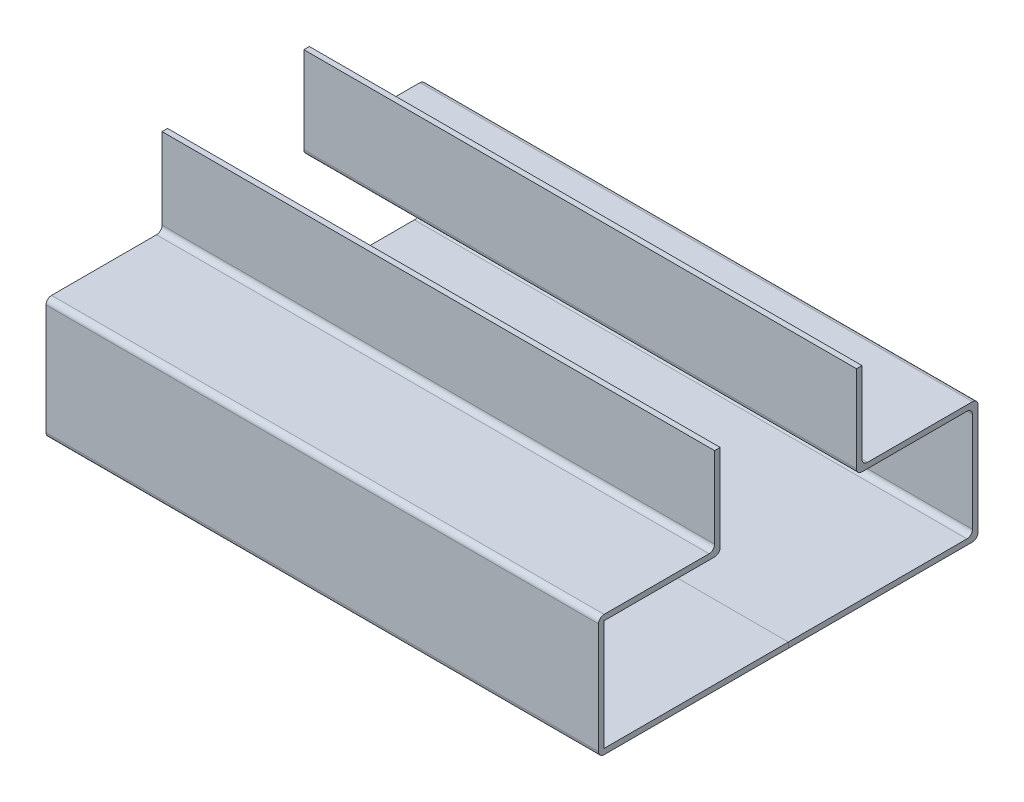
SolidWorks part; units mm, degrees
ref_plane "前基準面" through (0, 0, 0) normal (0, 0, 1) x (1, 0, 0)
ref_plane "上基準面" through (0, 0, 0) normal (0, 1, 0) x (1, 0, 0)
ref_plane "右基準面" through (0, 0, 0) normal (1, 0, 0) x (0, 0, -1)
ref_plane "平面1"
sketch "草圖1" plane through (0, 0, 0) normal (1, 0, 0) x (0, 1, 0)
  line L0 (0, 51.5) -> (0, 50)
  line L1 (0, 50) -> (31.5, 50)
  line L2 (30, 51.5) -> (0, 51.5)
  line L3 (0, 0) -> (0, 51.5)
  line L4 (-1.5, 50) -> (-1.5, 0)
  line L5 (-1.5, 0) -> (0, 0)
  line L6 (31.5, 50) -> (30, 50)
  line L7 (30, 50) -> (30, 18.5)
  line L8 (30, 18.5) -> (31.5, 18.5)
  line L9 (31.5, 18.5) -> (55, 18.5)
  line L10 (55, 18.5) -> (55, 20)
  line L11 (55, 20) -> (33, 20)
  line L12 (31.5, 21.5) -> (31.5, 50)
  arc A0 (31.5, 50) -> (30, 51.5) centre (30, 50) ccw
  arc A1 (0, 51.5) -> (-1.5, 50) centre (0, 50) ccw
  arc A2 (31.5, 21.5) -> (33, 20) centre (33, 21.5) ccw
extrude "擠出1" add sketch "草圖1" along normal blind 75 and the other way blind 75 contours L1 A0 L2 L0 | L0 A1 L4 L5 L3 | A2 L12 L1 L7 L8 L9 L10 L11 region at (0, 15.5908, 50.7457) region at (0, -0.7474, 25.5901) region at (0, 30.75, 49.5978)
ref_plane "平面2" through (15, -0.75, 0) normal (0, 0, -1) x (0, 1, 0)
mirror "鏡射1" about plane through (15, -0.75, 0) normal (0, 0, -1) of bodies 101
sketch "草圖2" plane through (0, 55, 0) normal (0, 1, 0) x (-1, 0, 0)
  line L0 (-76.5, 0.5) -> (-76.5, 2)
  line L1 (-76.5, 2) -> (-86.5, 2)
  line L2 (-86.5, 2) -> (-86.5, 0.5)
  line L3 (-86.5, 0.5) -> (-76.5, 0.5)
  line L4 (-75, 20) -> (-76.5, 20)
  line L5 (-76.5, 20) -> (-76.5, 0.5)
  line L6 (-76.5, 0.5) -> (-75, 0.5)
  line L7 (-75, 0.5) -> (-75, 20)
  dimension "D1" = 1.5
  dimension "D2" = 19.5
  dimension "D3" = 10
  dimension "D4" = 1.5
extrude "擠出2" add sketch "草圖2" rebuild error yes
ref_plane "平面3" through (86.5, 31, 2) normal (0, 0, 1) x (1, 0, 0)
sketch "草圖3" plane through (86.5, 31, 2) normal (0, 0, 1) x (1, 0, 0)
  circle A0 centre (-5, 12) radius 2.5
  dimension "D1" = 5
extrude "擠出3" sketch "草圖3" rebuild error yes
ref_plane "平面4" through (0, 0, 0) normal (1, 0, 0) x (0, 1, 0)
mirror "鏡射2" rebuild error yes
ref_plane "平面5" through (0, 0, 0) normal (0, 0, 1) x (1, 0, 0)
mirror "鏡射3" about plane through (0, 0, 0) normal (0, 0, 1) rebuild error yes
fillet "圓角2" radius 1.5 1 edges at (0, 30, 18.5)
fillet "圓角3" radius 1.5 1 edges at (0, 30, -18.5)
fillet "圓角7" radius 1.5 2 edges at (0, 0, -50) (0, 30, -50)
sketch "草圖4" plane through (75, 0, 0) normal (1, 0, 0) x (0, 0, -1)
  line L0 (-50, -1.5) -> (50, -1.5)
  line L1 (50, -1.5) -> (50, 28.5)
  line L2 (50, 28.5) -> (-50, 28.5)
  line L3 (-50, 28.5) -> (-50, -1.5)
extrude "擠出4" add sketch "草圖4" rebuild error yes
ref_plane "平面6" through (0, 0, 0) normal (1, 0, 0) x (0, 1, 0)
mirror "鏡射4" about plane through (0, 0, 0) normal (1, 0, 0) rebuild error yes
